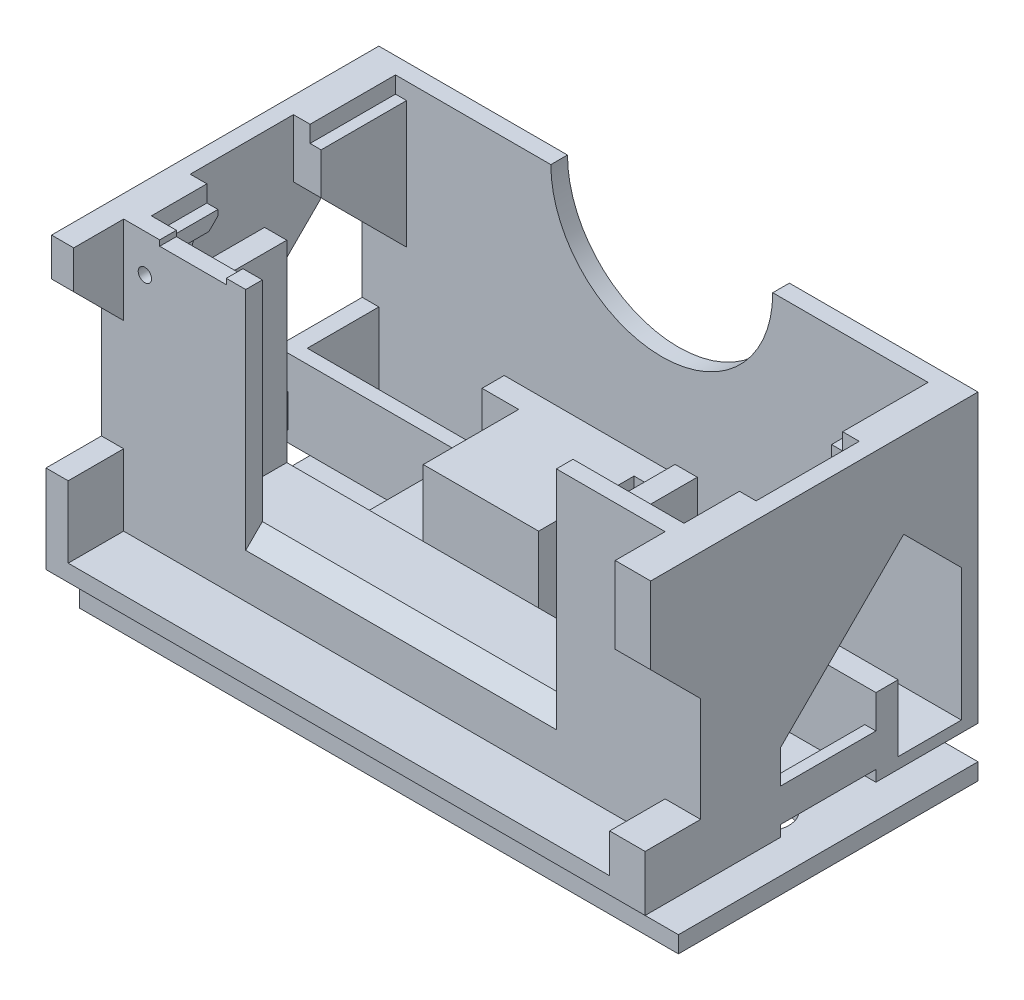
SolidWorks part; units mm, degrees
ref_plane "Front Plane" through (0, 0, 0) normal (0, 0, 1) x (1, 0, 0)
ref_plane "Top Plane" through (0, 0, 0) normal (0, 1, 0) x (1, 0, 0)
ref_plane "Right Plane" through (0, 0, 0) normal (1, 0, 0) x (0, 0, -1)
sketch "Sketch1" plane through (0, 0, 0) normal (0, 1, 0) x (1, 0, 0)
  line L1 (0, 0) -> (54, 0)
  line L2 (0, 0) -> (0, 27)
  line L3 (0, 27) -> (54, 27)
  line L4 (54, 0) -> (54, 27)
  dimension "D1" = 54
  dimension "D2" = 27
extrude "Boss-Extrude1" add sketch "Sketch1" along normal blind 1.5
sketch "Sketch2" plane through (0, 1.5, 0) normal (0, 1, 0) x (1, 0, 0)
  line L0 (0, 27) -> (0, 0) construction
  circle A0 centre (5.8, 13.5) radius 2.25
  point P5 (0, 13.5)
  dimension "D3" = 4.5
  dimension "D1" = 5.8
extrude "Cut-Extrude1" cut sketch "Sketch2" against normal up to next and the other way through all
ref_plane "Plane1" through (27, 0, 0) normal (-1, 0, 0) x (0, 0, 1)
mirror "Mirror1" about plane through (27, 0, 0) normal (-1, 0, 0) of "Cut-Extrude1"
sketch "Sketch3" plane through (0, 1.5, 0) normal (0, 1, 0) x (1, 0, 0)
  line L0 (54, 27) -> (0, 27) construction
  line L1 (13.8, 27) -> (40.2, 27)
  line L2 (13.8, 27) -> (13.8, -3)
  line L3 (13.8, -3) -> (40.2, -3)
  line L4 (40.2, 27) -> (40.2, -3)
  line L7 (0, 0) -> (54, 0) construction
  circle A0 centre (5.8, 13.5) radius 2.25 construction
  point P8 (27, 0)
  point P9 (27, -3)
  dimension "D1" = 8
  dimension "D2" = 3
extrude "Boss-Extrude2" add sketch "Sketch3" along normal blind 3
chamfer "Chamfer3" distance 3 angle 45 1 edges at (27, 1.5, 3)
sketch "Sketch4" plane through (0, 4.5, 0) normal (0, 1, 0) x (1, 0, 0)
  line L0 (54, 0) -> (54, 27) construction
  line L1 (0, 27) -> (54, 27)
  line L2 (0, 27) -> (0, 2)
  line L3 (0, 2) -> (54, 2)
  line L4 (54, 27) -> (54, 2)
  line L5 (0, 27) -> (0, 0) construction
  line L6 (0, 17.8) -> (54, 17.8)
  line L7 (0, 17.8) -> (0, 9.2)
  line L8 (0, 9.2) -> (54, 9.2)
  line L9 (54, 17.8) -> (54, 9.2)
  line L10 (40.2, 27) -> (13.8, 27) construction
  line L11 (0, 27) -> (0, 0) construction
  line L13 (32.2, 17.8) -> (21.8, 17.8)
  line L14 (32.2, 17.8) -> (32.2, 9.2)
  line L15 (32.2, 9.2) -> (21.8, 9.2)
  line L16 (21.8, 17.8) -> (21.8, 9.2)
  line L17 (40.2, 0) -> (54, 0) construction
  point P0 (0, 13.5)
  point P17 (0, 13.5)
  point P23 (27, 17.8)
  point P24 (27, 17.8)
  line M9 (13.8, 27) -> (13.8, -3)
  line M11 (40.2, -3) -> (40.2, 27)
  line M12 (40.2, 27) -> (13.8, 27)
  dimension "D1" = 8.6
  dimension "D2" = 21.8
  dimension "D3" = 2
extrude "Boss-Extrude3" add sketch "Sketch4" along normal blind 7 contours L2 L6 L1 M9 | L6 M9 M11 M12 | L6 L4 L1 M11 | L8 L3 L4 M11 | L8 M9 M11 | L8 L2 L3 M9 | L14 L13 L16 L15 region at (6.9, 4.5, -22.4) region at (27, 4.5, -22.4) region at (47.1, 4.5, -22.4) region at (6.9, 4.5, -5.6) region at (27, 4.5, -5.6) region at (47.1, 4.5, -5.6)
sketch "Sketch25" plane through (54, 0, 0) normal (1, 0, 0) x (0, 0, -1)
  line L0 (17.8, 11.5) -> (17.8, 4.5) construction
  line L1 (9.2, 5.5) -> (17.8, 5.5)
  line L2 (9.2, 5.5) -> (9.2, 8.5)
  line L3 (9.2, 8.5) -> (17.8, 8.5)
  line L4 (17.8, 5.5) -> (17.8, 8.5)
  line L5 (9.2, 4.5) -> (2, 4.5) construction
  dimension "D1" = 4
  dimension "D2" = 1
extrude "Boss-Extrude19" add sketch "Sketch25" against normal blind 1
mirror "Mirror6" about plane through (27, 0, 0) normal (-1, 0, 0) of "Boss-Extrude19"
extrude "Boss-Extrude15" add sketch "Sketch4<4>" along normal blind 6 from surface contours L6 L16 L8 L14 region at (27, 4.5, -13.5) starting at face at (27, 11.5, -13.8333)
sketch "Sketch4<4>" plane through (0, 4.5, 0) normal (0, 1, 0) x (1, 0, 0) same geometry as "Sketch4"
sketch "Sketch5" plane through (0, 11.5, 0) normal (0, 1, 0) x (1, 0, 0)
  line L0 (54, 9.2) -> (54, 2) construction
  line L1 (54, 2) -> (0, 2)
  line L2 (54, 2) -> (54, 3.5)
  line L3 (54, 3.5) -> (0, 3.5)
  line L4 (0, 2) -> (0, 3.5)
  line L5 (0, 9.2) -> (0, 2) construction
  line L6 (32.2, 9.2) -> (54, 9.2) construction
  line L7 (27, 0.825) -> (27, -0.825) construction
  line L16 (9.5, 9.2) -> (7.5, 9.2)
  line L17 (44.5, 3.5) -> (46.5, 3.5)
  line L18 (44.5, 3.5) -> (44.5, 9.2)
  line L19 (44.5, 9.2) -> (46.5, 9.2)
  line L20 (46.5, 3.5) -> (46.5, 9.2)
  line L21 (7.5, 3.5) -> (7.5, 9.2)
  line L22 (9.5, 3.5) -> (7.5, 3.5)
  line L23 (9.5, 3.5) -> (9.5, 9.2)
  line L27 (52.225, 2) -> (46.225, 2)
  line L29 (1.775, 2) -> (7.775, 2)
  line L33 (0, 27) -> (0, 17.8) construction
  line L34 (54, 27) -> (0, 27)
  line L35 (54, 27) -> (54, 25.5)
  line L36 (54, 25.5) -> (0, 25.5)
  line L37 (0, 27) -> (0, 25.5)
  line M16 (21.8, 9.2) -> (0, 9.2)
  line M20 (54, 9.2) -> (32.2, 9.2)
  dimension "D1" = 22
  dimension "D2" = 1.5
  dimension "D3" = 19.5
  dimension "D4" = 2
  dimension "D7" = 1.5
extrude "Boss-Extrude5" add sketch "Sketch5" along normal offset from surface (18.86 mm away) 25.86 contours L3 L4 L1 L2 up to face at (27, 4.5, 0.5) offset beyond the face yes
extrude "Boss-Extrude6" add sketch "Sketch5<3>" along normal offset from surface (17.36 mm away) 1.5 contours L3 L20 L18 M20 | L3 L23 L21 M16 region at (45.5, 11.5, -6.35) region at (8.5, 11.5, -6.35) up to face at (27, 30.36, -2.75)
sketch "Sketch5<3>" plane through (0, 11.5, 0) normal (0, 1, 0) x (1, 0, 0) same geometry as "Sketch5"
extrude "Boss-Extrude12" add sketch "Sketch4<3>" along normal offset from surface (3.86 mm away) 20.5 contours L16 L6 L8 M9 | L6 L14 L8 M11 region at (17.8, 4.5, -13.5) region at (36.2, 4.5, -13.5) up to face at (45.5, 28.86, -6.35)
sketch "Sketch4<3>" plane through (0, 4.5, 0) normal (0, 1, 0) x (1, 0, 0) same geometry as "Sketch4"
sketch "Sketch17" plane through (0, 0, -2) normal (0, 0, 1) x (1, 0, 0)
  line L0 (54, 30.36) -> (54, 4.5) construction
  line L1 (0, 4.5) -> (54, 4.5)
  line L2 (0, 4.5) -> (0, 6)
  line L3 (0, 6) -> (54, 6)
  line L4 (54, 4.5) -> (54, 6)
  line L5 (54, 30.36) -> (0, 30.36) construction
  line L10 (0, 30.36) -> (2, 30.36)
  line L11 (0, 30.36) -> (0, 6)
  line L12 (0, 6) -> (2, 6)
  line L13 (2, 30.36) -> (2, 6)
  line L14 (2, 22.43) -> (0, 22.43)
  line L15 (2, 22.43) -> (2, 12.43)
  line L16 (2, 12.43) -> (0, 12.43)
  line L17 (0, 22.43) -> (0, 12.43)
  line L23 (54, 6) -> (50.8, 6)
  line L24 (54, 30.36) -> (50.8, 30.36)
  line L25 (54, 30.36) -> (54, 18.93)
  line L26 (54, 18.93) -> (50.8, 18.93)
  line L27 (50.8, 30.36) -> (50.8, 18.93)
  line L28 (54, 6) -> (54, 9.5)
  line L29 (54, 9.5) -> (50.8, 9.5)
  line L30 (50.8, 6) -> (50.8, 9.5)
  point P18 (2, 17.43)
  point P20 (52.4, 18.93)
  line M21 (0, 4.5) -> (13.8, 4.5)
  line M22 (13.8, 4.5) -> (40.2, 4.5)
  line M23 (40.2, 4.5) -> (54, 4.5)
  line M24 (54, 4.5) -> (54, 30.36)
  line M25 (54, 30.36) -> (0, 30.36)
  line M26 (0, 30.36) -> (0, 4.5)
  dimension "D1" = 1.5
  dimension "D2" = 48.8
  dimension "D3" = 2
  dimension "D4" = 10
  dimension "D5" = 11.43
  dimension "D6" = 11.43
  dimension "D7" = 5
extrude "Boss-Extrude13" add sketch "Sketch17" along normal up to vertex (5 mm away) contours L13 L16 L3 M26 | L3 M26 M21 M22 M23 M24 | L28 L23 L30 L29 region at (27, 5.25, -2) region at (1, 9.215, -2) up to point (13.8, 4.5, 3)
extrude "Boss-Extrude16" add sketch "Sketch17<3>" along normal offset from surface (4.5 mm away) 0.5 contours L14 L13 M25 M26 | L27 L26 M25 M24 region at (1, 26.395, -2) region at (52.4, 24.645, -2) up to face at (26.76, 7.386, 3)
sketch "Sketch17<3>" plane through (0, 0, -2) normal (0, 0, 1) x (1, 0, 0) same geometry as "Sketch17"
chamfer "Chamfer7" distance 4.5 angle 45 2 edges at (52.4, 18.93, 2.5) (1, 22.43, 2.5)
extrude "Boss-Extrude8" add sketch "Sketch5<4>" along normal up to surface (18.86 mm away) contours L36 region at (27, 11.5, -26.25) up to face at (26.7, 30.36, -0.125)
sketch "Sketch5<4>" plane through (0, 11.5, 0) normal (0, 1, 0) x (1, 0, 0) same geometry as "Sketch5"
sketch "Sketch10" plane through (0, 0, 0) normal (-1, 0, 0) x (0, 0, 1)
  line L0 (-3.5, 30.36) -> (-25.5, 30.36)
  line L1 (-3.5, 30.36) -> (-3.5, 11.5) construction
  line L2 (-25.5, 30.36) -> (-25.5, 11.5) construction
  line L3 (-25.5, 30.36) -> (-25.5, 11.5)
  line L6 (-3.5, 11.5) -> (-3.5, 30.36)
  line L8 (-9.2, 11.5) -> (-3.5, 11.5) construction
  line L9 (-3.5, 30.36) -> (-9.2, 30.36)
  line L10 (-3.5, 30.36) -> (-3.5, 11.5)
  line L11 (-3.5, 11.5) -> (-9.2, 11.5)
  line L12 (-9.2, 30.36) -> (-9.2, 11.5)
  line L13 (-9.2, 28.86) -> (-9.2, 11.5) construction
  line L14 (-25.5, 11.5) -> (-17.8, 11.5) construction
  line L15 (-25.5, 30.36) -> (-19.35, 30.36)
  line L16 (-25.5, 30.36) -> (-25.5, 11.5)
  line L17 (-25.5, 11.5) -> (-19.35, 11.5)
  line L19 (2.5, 30.36) -> (-3.5, 30.36) construction
  line L21 (-25.5, 27.8) -> (-9.2, 11.5)
  line M36 (-3.5, 30.36) -> (-3.5, 11.5)
  line M37 (-3.5, 11.5) -> (-9.2, 11.5)
  dimension "D1" = 0
  dimension "D4" = 45
extrude "Boss-Extrude9" add sketch "Sketch10" against normal blind 1.5 contours L0 L12 M37 M36 | L16 L21 L12 L0 region at (0, 20.93, -6.35) region at (0, 23.9713, -15.2827)
mirror "Mirror3" about plane through (27, 0, 0) normal (-1, 0, 0) of "Boss-Extrude9"
sketch "Sketch18" plane through (0, 30.36, 0) normal (0, 1, 0) x (1, 0, 0)
  line L0 (52.5, 25.5) -> (1.5, 25.5) construction
  line L1 (0, 25.5) -> (4, 25.5)
  line L2 (0, 25.5) -> (0, 17.8)
  line L3 (0, 17.8) -> (4, 17.8)
  line L4 (4, 25.5) -> (4, 17.8)
  line L5 (27, 0.825) -> (27, -0.825) construction
  line L6 (52.5, 8.5) -> (50, 8.5)
  line L7 (1.5, 3.5) -> (4, 3.5)
  line L8 (0, 17.8) -> (21.8, 17.8) construction
  line L9 (54, 17.8) -> (50, 17.8)
  line L10 (50, 25.5) -> (50, 17.8)
  line L11 (54, 25.5) -> (50, 25.5)
  line L12 (54, 25.5) -> (54, 17.8)
  line L13 (0, -2.5) -> (0, 27) construction
  line L14 (1.5, 3.5) -> (1.5, 8.5)
  line L15 (1.5, 8.5) -> (4, 8.5)
  line L16 (4, 3.5) -> (4, 8.5)
  line L17 (50, 3.5) -> (50, 8.5)
  line L18 (52.5, 3.5) -> (50, 3.5)
  line L19 (52.5, 3.5) -> (52.5, 8.5)
  line M5 (52.5, 25.5) -> (52.5, 3.5)
  line M6 (52.5, 3.5) -> (1.5, 3.5)
  line M8 (1.5, 25.5) -> (52.5, 25.5)
  line M10 (0, 27) -> (0, -2.5)
  line M16 (54, -2.5) -> (54, 27)
  dimension "D1" = 23
  dimension "D2" = 5
extrude "Boss-Extrude14" add sketch "Sketch18" against normal blind 13 contours L11 L9 M16 M5 | L10 L9 M8 M5 | L4 L3 M8 | L3 L1 M10 | L4 L3 L2 L1 region at (51.25, 30.36, -21.65) region at (2, 30.36, -21.65) region at (53.25, 30.36, -21.65)
extrude "Boss-Extrude17" add sketch "Sketch18<3>" against normal blind 7 contours L16 L15 M6 | L17 L6 M6 M5 region at (51.25, 30.36, -6) region at (2.75, 30.36, -6)
sketch "Sketch18<3>" plane through (0, 30.36, 0) normal (0, 1, 0) x (1, 0, 0) same geometry as "Sketch18"
chamfer "Chamfer8" distance 5 angle 45 2 edges at (51.25, 23.36, -8.5) (2.75, 23.36, -8.5)
chamfer "Chamfer6" distance 7.75 angle 45 2 edges at (2, 17.36, -17.8) (52, 17.36, -17.8)
sketch "Sketch20" plane through (0, 30.36, 0) normal (0, 1, 0) x (1, 0, 0)
  line L0 (0, 17.8) -> (21.8, 17.8) construction
  line L1 (4, 25.5) -> (3, 25.5)
  line L2 (4, 25.5) -> (4, 17.8)
  line L3 (4, 17.8) -> (3, 17.8)
  line L4 (3, 25.5) -> (3, 17.8)
  line L5 (27, 0.825) -> (27, -0.825) construction
  line L6 (50, 17.8) -> (51, 17.8)
  line L7 (51, 25.5) -> (51, 17.8)
  line L8 (50, 25.5) -> (51, 25.5)
  line L9 (50, 25.5) -> (50, 17.8)
  line L10 (50, 3.5) -> (4, 3.5) construction
  line L11 (4, 8.5) -> (3, 8.5)
  line L12 (4, 8.5) -> (4, 3.5)
  line L13 (4, 3.5) -> (3, 3.5)
  line L14 (3, 8.5) -> (3, 3.5)
  line L15 (50, 3.5) -> (51, 3.5)
  line L16 (51, 8.5) -> (51, 3.5)
  line L17 (50, 8.5) -> (51, 8.5)
  line L18 (50, 8.5) -> (50, 3.5)
  dimension "D1" = 1
  dimension "D2" = 1
extrude "Cut-Extrude7" cut sketch "Sketch20" against normal up to surface (1.5 mm away) up to face at (8.5, 28.86, -6.35)
sketch "Sketch22" plane through (0, 30.36, 0) normal (0, 1, 0) x (1, 0, 0)
  line L0 (50.8, 2) -> (2, 2) construction
  line L1 (5.25, 2) -> (11.25, 2)
  line L2 (5.25, 2) -> (5.25, 3.5)
  line L3 (5.25, 3.5) -> (11.25, 3.5)
  line L4 (11.25, 2) -> (11.25, 3.5)
  line L5 (51, 3.5) -> (3, 3.5) construction
  line L6 (3, 8.5) -> (3, 3.5) construction
  dimension "D1" = 6
  dimension "D2" = 2.25
extrude "Cut-Extrude10" cut sketch "Sketch22" against normal offset from surface (0.5 mm away) 1 up to face at (8.5, 28.86, -6.35)
sketch "Sketch12" plane through (0, 0, -2) normal (0, 0, 1) x (1, 0, 0)
  line L1 (13, 30.36) -> (41, 30.36)
  line L3 (13, 30.36) -> (13, 11.5)
  line L4 (13, 11.5) -> (41, 11.5)
  line L5 (41, 30.36) -> (41, 11.5)
  line L6 (52.5, 30.36) -> (1.5, 30.36) construction
  line L7 (44.5, 11.5) -> (9.5, 11.5) construction
  point P11 (27, 30.36)
  point P12 (27, 30.36)
  dimension "D1" = 28
extrude "Cut-Extrude2" cut sketch "Sketch12" against normal up to surface (7.2 mm away) up to face at (46.7533, 11.2627, -9.2)
sketch "Sketch14" plane through (0, 0, -27) normal (0, 0, -1) x (-1, 0, 0)
  line L1 (-54, 30.36) -> (0, 30.36) construction
  line L2 (-37, 30.36) -> (-17, 30.36)
  line L4 (-37, 30.36) -> (-17, 30.36)
  circle A1 centre (-27, 30.36) radius 10
  point P4 (-27, 30.36)
  point P7 (-27, 30.36)
  point P11 (-27, 30.36)
  line M7 (0, 30.36) -> (-54, 30.36)
  dimension "D1" = 20
extrude "Cut-Extrude3" cut sketch "Sketch14" against normal up to next contours A1 M7 | A1 region at (27, 26.1159, -27)
sketch "Sketch15" plane through (0, 11.5, 0) normal (0, 1, 0) x (1, 0, 0)
  line L0 (54, 25.5) -> (54, 17.8) construction
  line L1 (27.5, 17.8) -> (18.5, 17.8)
  line L2 (27.5, 17.8) -> (27.5, 19.8)
  line L3 (27.5, 19.8) -> (18.5, 19.8)
  line L4 (18.5, 17.8) -> (18.5, 19.8)
  line L6 (54, 25.5) -> (0, 25.5) construction
  line L7 (0, 17.8) -> (21.8, 17.8) construction
  dimension "D1" = 35.5
  dimension "D2" = 9
  dimension "D4" = 5.7
extrude "Boss-Extrude11" add sketch "Sketch15" along normal blind 6
mirror "Mirror5" about plane through (27, 0, 0) normal (-1, 0, 0) of "Boss-Extrude11"
sketch "Sketch21" plane through (0, 11.5, 0) normal (0, 1, 0) x (1, 0, 0)
  line L0 (54, 25.5) -> (54, 17.8) construction
  line L1 (0, 25.5) -> (54, 25.5)
  line L2 (0, 25.5) -> (0, 19.8)
  line L3 (0, 19.8) -> (54, 19.8)
  line L4 (54, 25.5) -> (54, 19.8)
  line L5 (18.5, 19.8) -> (35.5, 19.8) construction
  line L6 (18.5, 19.8) -> (18.5, 17.8) construction
  line L7 (0, 25.5) -> (18.5, 25.5)
  line L8 (0, 25.5) -> (0, 19.05)
  line L9 (0, 19.05) -> (18.5, 19.05)
  line L10 (18.5, 25.5) -> (18.5, 19.05)
  line M6 (18.5, 19.8) -> (35.5, 19.8)
  line M9 (54, 17.8) -> (54, 25.5)
  line M10 (54, 25.5) -> (0, 25.5)
  line M11 (0, 25.5) -> (0, 17.8)
  line M13 (18.5, 17.8) -> (18.5, 19.8)
  line M14 (18.5, 19.8) -> (35.5, 19.8)
  dimension "D1" = 0.75
extrude "Cut-Extrude8" cut sketch "Sketch21" against normal blind 6 contours L10 L3 M10 M14 M6 M9 | L10 L1 L3 M11 | L9 L3 M11 M13 region at (9.25, 11.5, -22.65) region at (36.25, 11.5, -22.65) region at (9.25, 11.5, -19.425)
extrude "Cut-Extrude9" cut sketch "Sketch21<3>" against normal up to surface (7 mm away) from surface contours L10 L1 L3 M11 | L9 L3 M11 M13 region at (9.25, 11.5, -22.65) region at (9.25, 11.5, -19.425) up to face at (6.9, 4.5, -22.4) starting at face at (24.1667, 5.5, -21.45)
sketch "Sketch21<3>" plane through (0, 11.5, 0) normal (0, 1, 0) x (1, 0, 0) same geometry as "Sketch21"
fillet "Fillet7" radius 1 2 edges at (1.5, 17.43, -3.5) (52.5, 17.43, -3.5)
sketch "Sketch23" plane through (0, 0, -2) normal (0, 0, 1) x (1, 0, 0)
  line L0 (2, 30.36) -> (2, 22.43) construction
  line L1 (50.8, 30.36) -> (50.8, 18.93) construction
  line L2 (2, 6) -> (50.8, 6) construction
  circle A0 centre (3.91, 26.95) radius 0.6
  circle A1 centre (48.89, 26.95) radius 0.6
  dimension "D1" = 1.2
  dimension "D2" = 1.91
  dimension "D3" = 1.91
  dimension "D4" = 20.95
extrude "Cut-Extrude11" cut sketch "Sketch23" against normal up to next
chamfer "Chamfer9" distance 1.5 angle 45 1 edges at (27, 11.5, -2)
sketch "Sketch24" plane through (0, 0, -19.05) normal (0, 0, -1) x (-1, 0, 0)
  line L0 (-13.8, 4.5) -> (0, 4.5) construction
  line L1 (0, 11.5) -> (-1.5, 11.5)
  line L2 (0, 11.5) -> (0, 4.5)
  line L3 (0, 4.5) -> (-1.5, 4.5)
  line L4 (-1.5, 11.5) -> (-1.5, 4.5)
  line L5 (0, 4.5) -> (0, 11.5) construction
  dimension "D1" = 1.5
extrude "Boss-Extrude18" add sketch "Sketch24" along normal up to next
